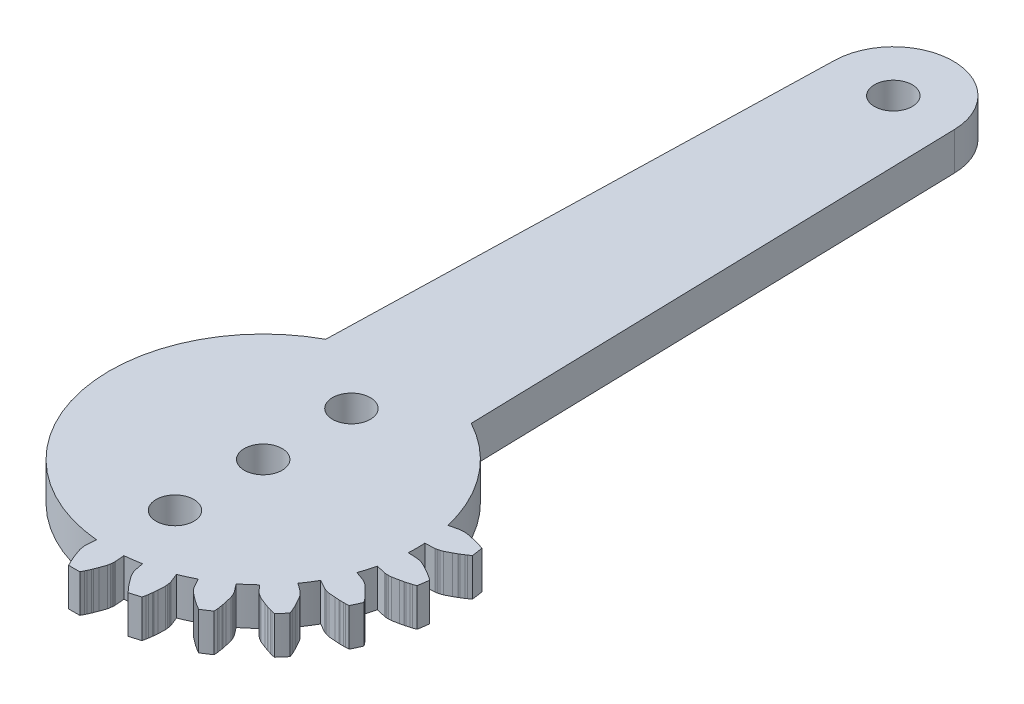
SolidWorks part; units mm, degrees
material "普通碳钢"
ref_plane "前视" through (0, 0, 0) normal (0, 0, 1) x (1, 0, 0)
ref_plane "上视" through (0, 0, 0) normal (0, 1, 0) x (1, 0, 0)
ref_plane "右视" through (0, 0, 0) normal (1, 0, 0) x (0, 0, -1)
sketch "草图1" plane through (0, 0, 0) normal (0, 1, 0) x (1, 0, 0)
  line L0 (39.751, 40.5224) -> (39.6866, 41.2679)
  line L1 (39.6866, 41.2679) -> (39.6851, 41.3287)
  line L2 (39.6851, 41.3287) -> (39.6859, 41.3577)
  line L3 (39.6859, 41.3577) -> (39.6916, 41.4528)
  line L4 (39.6916, 41.4528) -> (39.6929, 41.4698)
  line L5 (39.6929, 41.4698) -> (39.6966, 41.5042)
  line L6 (39.6966, 41.5042) -> (39.712, 41.6258)
  line L7 (39.712, 41.6258) -> (39.7121, 41.6267)
  line L8 (39.7121, 41.6267) -> (39.7482, 41.8247)
  line L9 (39.9295, 42.3366) -> (40.044, 42.6442)
  line L10 (40.044, 42.6442) -> (40.0454, 42.6478)
  line L11 (40.0454, 42.6478) -> (40.0855, 42.7398)
  line L12 (40.0855, 42.7398) -> (40.1995, 42.9971)
  line L13 (41.9203, 40.5224) -> (41.9848, 41.2679)
  line L14 (41.9848, 41.2679) -> (41.9862, 41.3287)
  line L15 (41.9862, 41.3287) -> (41.9855, 41.3577)
  line L16 (41.9855, 41.3577) -> (41.9797, 41.4528)
  line L17 (41.9797, 41.4528) -> (41.9784, 41.4698)
  line L18 (41.9784, 41.4698) -> (41.9748, 41.5042)
  line L19 (41.9748, 41.5042) -> (41.9594, 41.6258)
  line L20 (41.9594, 41.6258) -> (41.9592, 41.6267)
  line L21 (41.9592, 41.6267) -> (41.9231, 41.8247)
  line L22 (41.7419, 42.3366) -> (41.6274, 42.6442)
  line L23 (41.6274, 42.6442) -> (41.626, 42.6478)
  line L24 (41.626, 42.6478) -> (41.5858, 42.7398)
  line L25 (41.5858, 42.7398) -> (41.4718, 42.9971)
  circle A0 centre (40.8357, 28.3833) radius 12.1875 construction
  arc A1 (39.751, 40.5224) -> (41.9203, 40.5224) centre (40.8357, 28.3833) cw
  arc A2 (41.9231, 41.8247) -> (41.7419, 42.3366) centre (25.8953, 36.4382) ccw
  arc A4 (39.9295, 42.3366) -> (39.7482, 41.8247) centre (55.7761, 36.4382) ccw
  arc A5 (40.2653, 43.1347) -> (40.1995, 42.9971) centre (42.6892, 41.8899) ccw
  arc A6 (40.3945, 43.3768) -> (40.2653, 43.1347) centre (48.1168, 39.1026) ccw
  arc A11 (41.4718, 42.9971) -> (41.406, 43.1347) centre (38.9822, 41.8899) ccw
  arc A12 (41.406, 43.1347) -> (41.2769, 43.3768) centre (33.5546, 39.1026) ccw
  arc A13 (41.2769, 43.3768) -> (40.3945, 43.3768) centre (40.8357, 28.3833) ccw
  dimension "D1" = 24.375
extrude "凸台-拉伸1" add sketch "草图1" along normal blind 3 contours A4 L8 L7 L6 L5 L4 L3 L2 L1 L0 A1 L13 L14 L15 L16 L17 L18 L19 L20 L21 A2 L22 L23 L24 L25 A11 A12 A13 A6 A5 L12 L11 L10 L9
sketch "草图2" plane through (0, 0, 0) normal (0, -1, 0) x (1, 0, 0)
  circle A0 centre (40.8357, -28.3833) radius 12.1875
  circle A1 centre (40.8357, -28.3833) radius 1.5
  circle A2 centre (40.8357, -28.3833) radius 7 construction
  circle A3 centre (40.8357, -21.3833) radius 1.5
  circle A4 centre (40.8357, -35.3833) radius 1.5
  dimension "D1" = 3
  dimension "D2" = 24.375
  dimension "D3" = 14
  dimension "D4" = 3
  dimension "D5" = 3
extrude "凸台-拉伸2" add sketch "草图2" against normal blind 3
pattern_circular "阵列(圆周)2" count 22 over 360 about axis through (40.8357, 3, -28.3833) along (0, -1, 0) of "凸台-拉伸1"
sketch "草图3" plane through (0, 0, 0) normal (0, -1, 0) x (-1, 0, 0)
  circle A0 centre (-40.8357, 28.3833) radius 13.75
  dimension "D1" = 27.5
sketch "草图5" plane through (0, 0, 0) normal (0, -1, 0) x (1, 0, 0)
  line L0 (40.8357, -19.8833) -> (40.8357, -83.1349) construction
  line L1 (45.5857, -78.5069) -> (46.6107, -39.1157)
  line L2 (36.0857, -78.5069) -> (35.0607, -39.1157)
  circle A0 centre (40.8357, -21.3833) radius 1.5 construction
  circle A2 centre (40.8357, -28.3833) radius 12.1875 construction
  arc A3 (53.0056, -29.0373) -> (53.0056, -27.7293) centre (40.8357, -28.3833) ccw construction
  arc A4 (36.0857, -78.5069) -> (45.5857, -78.5069) centre (40.8357, -78.3833) ccw
  circle A5 centre (40.8357, -78.3833) radius 1.5
  arc A6 (35.0607, -39.1157) -> (46.6107, -39.1157) centre (40.8357, -28.3833) ccw
  dimension "D4" = 3
  dimension "D1" = 11.55
  dimension "D2" = 9.5
  dimension "D3" = 50
extrude "凸台-拉伸3" add sketch "草图5" against normal blind 3
sketch "草图7" plane through (0, 0, 0) normal (0, -1, 0) x (1, 0, 0)
  line L0 (36.0857, -78.5069) -> (35.0169, -37.4325) construction
  line L1 (35.0682, -39.4039) -> (36.0857, -78.5069) construction
  line L2 (45.5857, -78.5069) -> (46.6843, -36.2872) construction
  line L3 (45.5857, -78.5069) -> (46.6032, -39.4039) construction
  line L4 (35.0607, -39.1157) -> (35.0682, -39.4039)
  line L5 (35.0682, -39.4039) -> (34.8365, -39.8437)
  line L6 (34.8365, -39.8437) -> (33.6211, -45.0698)
  line L7 (33.6211, -45.0698) -> (23.2947, -35.4215)
  line L8 (23.2947, -35.4215) -> (25.1891, -22.1682)
  line L9 (25.1891, -22.1682) -> (31.4308, -11.204)
  line L10 (31.4308, -11.204) -> (37.9696, -9.817)
  line L11 (37.9696, -9.817) -> (39.751, -16.2441)
  line L12 (46.6107, -39.1157) -> (46.6032, -39.4039)
  line L13 (46.6032, -39.4039) -> (47.0142, -42.3632)
  line L14 (52.3284, -32.4394) -> (55.4375, -32.4394)
  line L15 (55.4375, -32.4394) -> (53.5277, -41.7128)
  line L16 (53.5277, -41.7128) -> (47.0142, -42.3632)
  arc A0 (35.0607, -39.1157) -> (39.751, -16.2441) centre (40.8357, -28.3833) cw
  circle A1 centre (40.8357, -28.3833) radius 1.5 construction
  circle A2 centre (40.8357, -28.3833) radius 12.1875 construction
  arc A3 (46.6107, -39.1157) -> (52.3284, -32.4394) centre (40.8357, -28.3833) ccw
extrude "切除-拉伸1" cut sketch "草图7" against normal blind 3
sketch "草图8" plane through (0, 0, 0) normal (0, -1, 0) x (-1, 0, 0)
  line L0 (-40.8357, 35.3833) -> (-40.8357, 21.3833)
